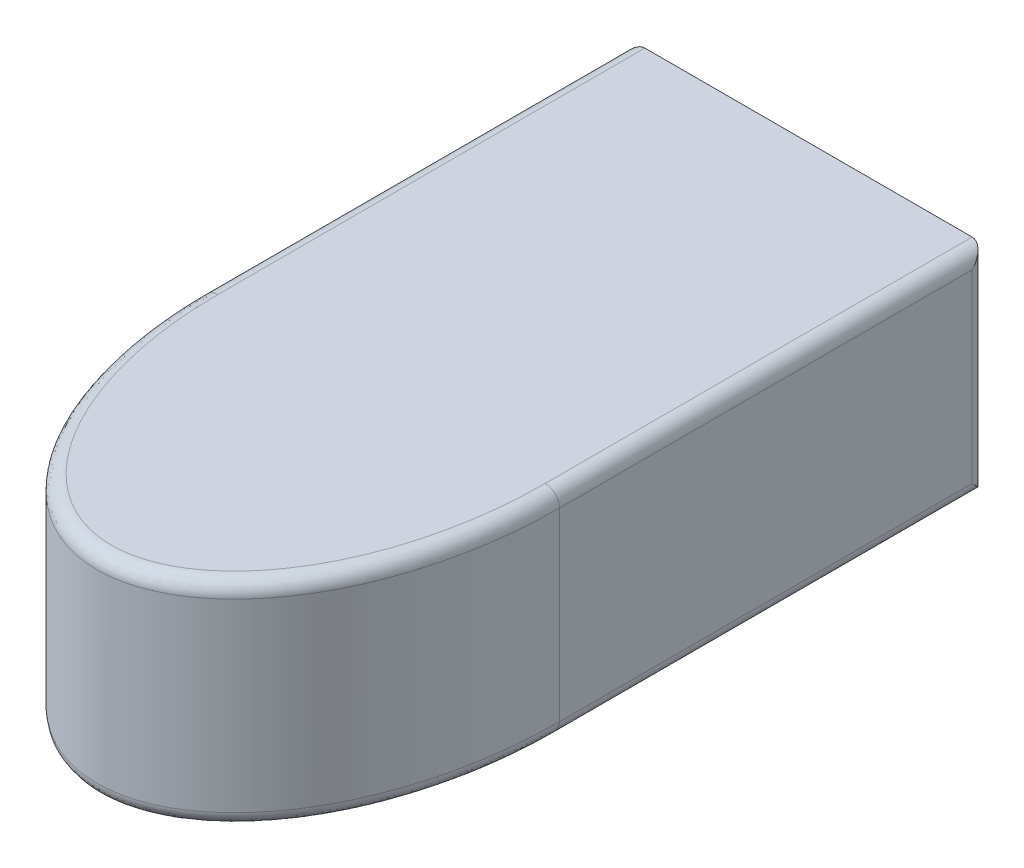
SolidWorks part; units mm, degrees
material "Nylon 101"
ref_plane "Front Plane" through (0, 0, 0) normal (0, 0, 1) x (1, 0, 0)
ref_plane "Top Plane" through (0, 0, 0) normal (0, 1, 0) x (1, 0, 0)
ref_plane "Right Plane" through (0, 0, 0) normal (1, 0, 0) x (0, 0, -1)
sketch "Sketch1" plane through (0, 0, 0) normal (0, 0, 1) x (1, 0, 0)
  line L1 (0, 4.4822) -> (0, 5.563) construction
  line L2 (0, 0) -> (-4.5658, 0) construction
  line L3 (12.5, -7.5) -> (-12.5, -7.5)
  line L4 (12.5, -7.5) -> (12.5, 7.5)
  line L5 (12.5, 7.5) -> (-12.5, 7.5)
  line L6 (-12.5, -7.5) -> (-12.5, 7.5)
  line L7 (12.5, -7.5) -> (-12.5, 7.5) construction
  line L8 (12.5, 7.5) -> (-12.5, -7.5) construction
  circle A0 centre (-8, 5) radius 1.1
  circle A1 centre (8, 5) radius 1.1
  circle A2 centre (8, -5) radius 1.1
  circle A3 centre (-8, -5) radius 1.1
  point P2 (0, 0)
  point P4 (0, 0)
  dimension "D3" = 2.2
  dimension "D1" = 8
  dimension "D2" = 5
  dimension "D4" = 25
  dimension "D5" = 15
extrude "base" add sketch "Sketch1" along normal blind 30 contours L6 L5 L4 L3
extrude "m2x10mm_pin" cut sketch "Sketch1<3>" along normal blind 5.1 contours A3 | A0 | A1 | A2
sketch "Sketch1<3>" plane through (0, 0, 0) normal (0, 0, 1) x (1, 0, 0) same geometry as "Sketch1"
sketch "Sketch2" plane through (0, -7.5, 0) normal (0, -1, 0) x (1, 0, 0)
  line L0 (12.5, 30) -> (-12.5, 30) construction
  line L1 (12.5, 30) -> (-12.5, 30)
  ellipse E0 centre (0, 30) end of major axis (0, 50) minor radius 12.5
  line M4 (12.5, 30) -> (-12.5, 30)
  dimension "D1" = 20
extrude "Boss-Extrude2" add sketch "Sketch2" against normal up to surface (15 mm away) contours E0 M4 region at (0, -7.5, 38.4883) up to face at (0, 7.5, 15)
fillet "Fillet1" radius 1 8 edges at (-12.5, 7.5, 15) (12.5, 7.5, 15) (12.5, -7.5, 15) (-12.5, -7.5, 15) (0, 7.5, 50) (0, -7.5, 50) (-12.5, 0, 0) (12.5, 0, 0)
